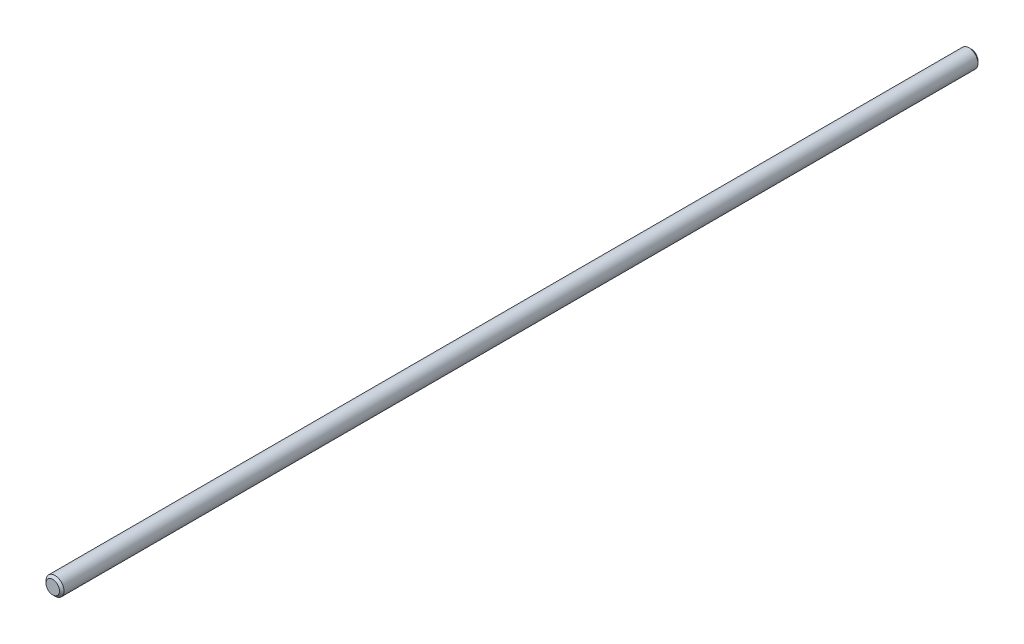
SolidWorks part; units mm, degrees
ref_plane "Front Plane" through (0, 0, 0) normal (0, 0, 1) x (1, 0, 0)
ref_plane "Top Plane" through (0, 0, 0) normal (0, 1, 0) x (1, 0, 0)
ref_plane "Right Plane" through (0, 0, 0) normal (1, 0, 0) x (0, 0, -1)
sketch "Sketch1" plane through (0, 0, 0) normal (0, 0, 1) x (1, 0, 0)
  circle A0 centre (0, 0) radius 4
  dimension "D1" = 8
extrude "Boss-Extrude1" add sketch "Sketch1" along normal blind 408
chamfer "Chamfer1" distance 1 angle 45 2 edges at (4, 0, 408) (4, 0, 0)
